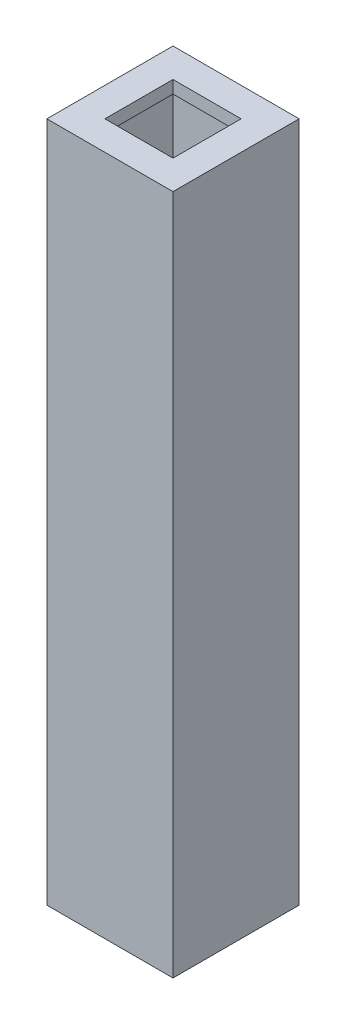
SolidWorks part; units mm, degrees
ref_plane "前视基准面" through (0, 0, 0) normal (0, 0, 1) x (1, 0, 0)
ref_plane "上视基准面" through (0, 0, 0) normal (0, 1, 0) x (1, 0, 0)
ref_plane "右视基准面" through (0, 0, 0) normal (1, 0, 0) x (0, 0, -1)
other "Configuration Table"
sketch "草图1" plane through (0, 0, 0) normal (0, 1, 0) x (1, 0, 0)
  line L1 (-3.1, 3.1) -> (3.1, 3.1)
  line L2 (-3.1, 3.1) -> (-3.1, -3.1)
  line L3 (-3.1, -3.1) -> (3.1, -3.1)
  line L4 (3.1, 3.1) -> (3.1, -3.1)
  line L5 (-3.1, 3.1) -> (3.1, -3.1) construction
  line L6 (-3.1, -3.1) -> (3.1, 3.1) construction
  line L7 (-5, 5) -> (5, 5)
  line L8 (-5, 5) -> (-5, -5)
  line L9 (-5, -5) -> (5, -5)
  line L10 (5, 5) -> (5, -5)
  line L11 (-5, 5) -> (5, -5) construction
  line L12 (-5, -5) -> (5, 5) construction
  line L13 (-2.7, -2.7) -> (2.7, -2.7)
  line L14 (-2.7, -2.7) -> (-2.7, 2.7)
  line L15 (-2.7, 2.7) -> (2.7, 2.7)
  line L16 (2.7, -2.7) -> (2.7, 2.7)
  line L17 (-2.7, -2.7) -> (2.7, 2.7) construction
  line L18 (-2.7, 2.7) -> (2.7, -2.7) construction
  point P0 (0, 0)
  point P5 (0, 0)
  point P13 (0, 0)
  dimension "D1" = 6.2
  dimension "D2" = 10
  dimension "D3" = 5.4
extrude "凸台-拉伸1" add sketch "草图1" along normal blind 54 contours L10 L7 L8 L9 L1 L4 L3 L2 region at (0, 0, -4.8586)
extrude "凸台-拉伸2" add sketch "草图1<3>" against normal blind 1 from surface contours L10 L7 L8 L9 L1 L4 L3 L2 | L4 L1 L2 L3 L16 L13 L14 L15 region at (0, 0, -3.0123) region at (0, 0, -4.8586) starting at face at (0, 54, 0)
sketch "草图1<3>" plane through (0, 0, 0) normal (0, 1, 0) x (1, 0, 0) same geometry as "草图1"
sketch "草图2" plane through (0, 0, 0) normal (0, -1, 0) x (1, 0, 0)
  line L0 (-5, 5) -> (-3, 3)
  line L1 (-3, -3) -> (3, -3)
  line L2 (-3, -3) -> (-3, 3)
  line L3 (-3, 3) -> (3, 3)
  line L4 (3, -3) -> (3, 3)
  line L5 (-3, -3) -> (3, 3) construction
  line L6 (-3, 3) -> (3, -3) construction
  line L7 (3, -3) -> (5, -5)
  circle A0 centre (-4, 4) radius 0.3
  circle A1 centre (4, -4) radius 0.3
  circle A2 centre (4, 4) radius 0.3
  circle A3 centre (-4, -4) radius 0.3
  point P0 (0, 0)
  dimension "D2" = 0.6
  dimension "D1" = 6
extrude "切除-拉伸1" cut sketch "草图2" against normal blind 2 contours A0 | A2 | A3 | A1
